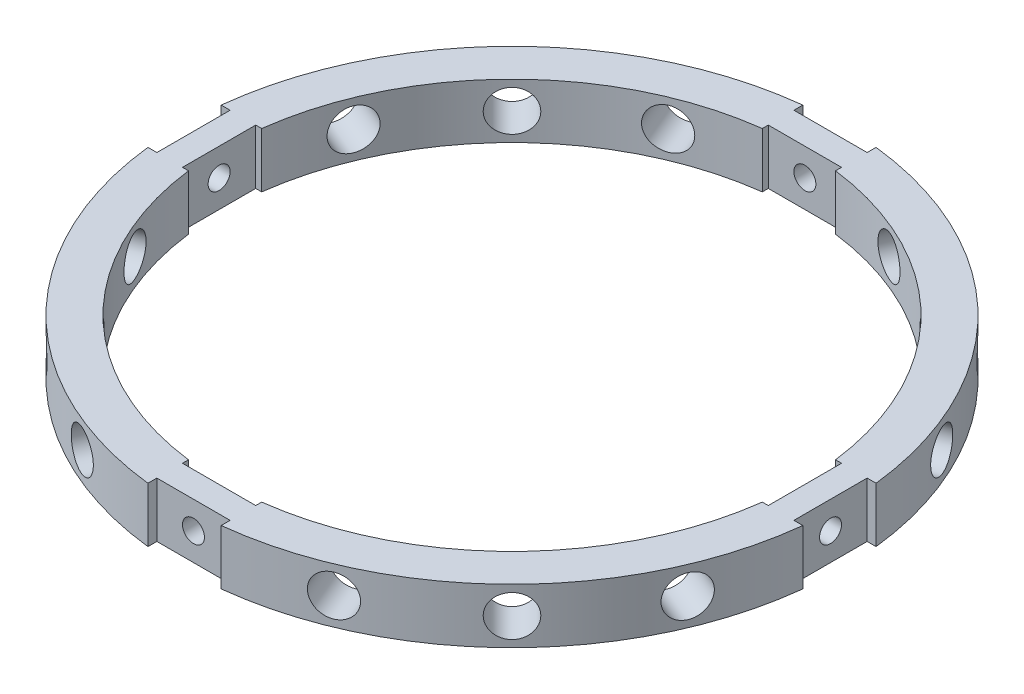
SolidWorks part; units mm, degrees
other "Markup1"
sketch "Sketch19"
material "1060 Alloy"
ref_plane "Front Plane" through (0, 0, 0) normal (0, 0, 1) x (1, 0, 0)
ref_plane "Top Plane" through (0, 0, 0) normal (0, 1, 0) x (1, 0, 0)
ref_plane "Right Plane" through (0, 0, 0) normal (1, 0, 0) x (0, 0, -1)
sketch "Sketch1" plane through (0, 0, 0) normal (0, 1, 0) x (1, 0, 0)
  circle A0 centre (0, 0) radius 90
  circle A1 centre (0, 0) radius 79
  dimension "OuterDiameter" = 180
  dimension "InnerDiameter" = 158
extrude "Boss-Extrude1" add sketch "Sketch1" along normal blind 7.5 and the other way blind 7.5
sketch "Sketch5" plane through (0, 7.5, 0) normal (0, 1, 0) x (1, 0, 0)
  line L0 (0, 0) -> (53.7588, 53.7588) construction
  line L1 (0.2616, 0.2616) -> (60.0121, 60.0121) construction
  line L2 (-121.3123, 0) -> (150.1577, 0) construction
  circle A0 centre (60.0121, 60.0121) radius 3
  circle A1 centre (60.0121, -59.4889) radius 3
  circle A2 centre (-59.4889, -59.4889) radius 3
  circle A3 centre (-59.4889, 60.0121) radius 3
  dimension "MountingBoltDiameter" = 6
  dimension "D2" = 84.5
  dimension "D3" = 45
sketch "Sketch6" plane through (0, 7.5, 0) normal (0, 1, 0) x (1, 0, 0)
  line L0 (0, -83.4209) -> (0, 77.0416) construction
  line L1 (-88.8703, 0) -> (103.6253, 0) construction
  line L2 (-10, -87) -> (10, -87)
  line L3 (-10, 90) -> (10, 90)
  line L4 (-10, 90) -> (-10, 87)
  line L5 (-10, 87) -> (10, 87)
  line L6 (10, 90) -> (10, 87)
  line L7 (-10, 90) -> (10, 87) construction
  line L8 (-10, 87) -> (10, 90) construction
  line L9 (10, -90) -> (10, -87)
  line L10 (-10, -90) -> (10, -90)
  line L11 (-10, -90) -> (-10, -87)
  line L12 (0, 0) -> (60.635, 60.635) construction
  line L13 (87, -10) -> (87, 10)
  line L14 (90, 10) -> (87, 10)
  line L15 (90, -10) -> (90, 10)
  line L16 (90, -10) -> (87, -10)
  line L17 (-90, -10) -> (-87, -10)
  line L18 (-90, -10) -> (-90, 10)
  line L19 (-90, 10) -> (-87, 10)
  line L20 (-87, -10) -> (-87, 10)
  point P5 (0, 88.5)
  point P10 (0, 90)
  dimension "RailWidth" = 20
  dimension "D1" = 90
  dimension "D2" = 3
extrude "Cut-Extrude4" cut sketch "Sketch6" against normal through all
sketch "Sketch7" plane through (-87, 0, 0) normal (-1, 0, 0) x (0, 0, 1)
  line L0 (0, 14.1508) -> (0, -8.7308) construction
  line L1 (-87, 0) -> (87, 0) construction
  line L2 (-87, -7.5) -> (-87, 7.5) construction
  line L3 (87, -7.5) -> (87, 7.5) construction
  circle A1 centre (0, 0) radius 3
  dimension "D1" = 6
extrude "Cut-Extrude5" cut sketch "Sketch7" against normal through all
sketch "Sketch12" plane through (0, 0, 87) normal (0, 0, 1) x (1, 0, 0)
  line L0 (0, 13.7216) -> (0, -16.0459) construction
  line L1 (-75.3828, 0) -> (78.5537, 0) construction
  circle A1 centre (0, 0) radius 3
  dimension "D1" = 6
extrude "Cut-Extrude8" cut sketch "Sketch12" against normal through all
sketch "Sketch13" plane through (0, 7.5, 0) normal (0, 1, 0) x (1, 0, 0)
  line L0 (0, -87.0356) -> (0, 86.4553) construction
  line L1 (-98.9563, 0) -> (122.4152, 0) construction
  line L2 (0, 0) -> (96.5387, 96.5387) construction
  line L3 (-10, -80) -> (10, -80)
  line L4 (-10, -80) -> (-10, -77)
  line L5 (-10, -77) -> (10, -77)
  line L6 (10, -80) -> (10, -77)
  line L7 (-10, -80) -> (10, -77) construction
  line L8 (-10, -77) -> (10, -80) construction
  line L9 (-10, 77) -> (10, 77)
  line L10 (10, 80) -> (10, 77)
  line L11 (-10, 80) -> (10, 80)
  line L12 (-10, 80) -> (-10, 77)
  line L13 (-77, -10) -> (-77, 10)
  line L14 (-80, 10) -> (-77, 10)
  line L15 (-80, -10) -> (-80, 10)
  line L16 (-80, -10) -> (-77, -10)
  line L17 (80, -10) -> (77, -10)
  line L18 (80, -10) -> (80, 10)
  line L19 (80, 10) -> (77, 10)
  line L20 (77, -10) -> (77, 10)
  point P7 (0, -78.5)
  dimension "D1" = 20
  dimension "D3" = 77
  dimension "D2" = 80
  dimension "D4" = 45
extrude "Cut-Extrude9" cut sketch "Sketch13" against normal through all
sketch "Sketch14" plane through (0, 7.5, 0) normal (0, 1, 0) x (1, 0, 0)
  line L0 (0, 98.1591) -> (0, -98.1685) construction
  line L1 (-142.6508, 0) -> (156.3484, 0) construction
  line L2 (0, -0.0047) -> (83.1508, 34.4375) construction
  line L3 (0, -0.0047) -> (34.4432, 83.1485) construction
  line L4 (-0.0047, 0) -> (83.1485, -34.4432) construction
  line L5 (-0.0047, 0) -> (34.4375, -83.1508) construction
  line L6 (0, 0.0047) -> (-34.4432, -83.1485) construction
  line L7 (0, 0.0047) -> (-83.1508, -34.4375) construction
  line L8 (0.0047, 0) -> (-83.1485, 34.4432) construction
  line L9 (0.0047, 0) -> (-34.4375, 83.1508) construction
  line L10 (63.6396, 63.6396) -> (-63.6396, -63.6396) construction
  line L11 (63.6396, -63.6396) -> (-63.6396, 63.6396) construction
  arc A0 (89.4427, 10) -> (10, 89.4427) centre (0, 0) ccw construction
  arc A1 (-89.4427, -10) -> (-10, -89.4427) centre (0, 0) ccw construction
  arc A2 (10, -89.4427) -> (89.4427, -10) centre (0, 0) ccw construction
  arc A3 (-10, 89.4427) -> (-89.4427, 10) centre (0, 0) ccw construction
  point P23 (0, 0)
  dimension "D1" = 22.5
  dimension "D2" = 22.5
  dimension "D3" = 4
ref_plane "Plane1" through (0.004, 0, -0.0017) normal (0.9239, 0, -0.3827) x (-0.3827, 0, -0.9239)
ref_plane "Plane2" through (0.0007, 0, -0.0017) normal (0.3827, 0, -0.9239) x (-0.9239, 0, -0.3827)
ref_plane "Plane3" through (-0.0017, 0, -0.004) normal (-0.3827, 0, -0.9239) x (-0.9239, 0, 0.3827)
ref_plane "Plane4" through (-0.0017, 0, -0.0007) normal (-0.9239, 0, -0.3827) x (-0.3827, 0, 0.9239)
sketch "Sketch15" plane through (0.004, 0, -0.0017) normal (0.9239, 0, -0.3827) x (-0.3827, 0, -0.9239)
  line L0 (-103.0218, 0) -> (121.7701, 0) construction
  circle A0 centre (0, 0) radius 5.565
  dimension "D1" = 11.13
extrude "Cut-Extrude10" cut sketch "Sketch15" against normal through all and the other way through all
sketch "Sketch16" plane through (0.0007, 0, -0.0017) normal (0.3827, 0, -0.9239) x (-0.9239, 0, -0.3827)
  line L0 (-116.6479, 0) -> (178.0546, 0) construction
  circle A0 centre (0, 0) radius 5.565
  dimension "D1" = 11.13
extrude "Cut-Extrude11" cut sketch "Sketch16" against normal through all and the other way through all
sketch "Sketch17" plane through (-0.0017, 0, -0.004) normal (-0.3827, 0, -0.9239) x (-0.9239, 0, 0.3827)
  line L0 (-115.4594, 0) -> (154.8622, 0) construction
  circle A0 centre (0, 0) radius 5.565
  dimension "D1" = 11.13
extrude "Cut-Extrude12" cut sketch "Sketch17" against normal through all and the other way through all
sketch "Sketch18" plane through (-0.0017, 0, -0.0007) normal (-0.9239, 0, -0.3827) x (-0.3827, 0, 0.9239)
  line L0 (-110.4319, 0) -> (111.3832, 0) construction
  circle A0 centre (0.4757, 0) radius 5.565
  dimension "D1" = 11.13
extrude "Cut-Extrude13" cut sketch "Sketch18" against normal through all and the other way through all
ref_plane "Plane5" through (0, 0, 0) normal (0.7071, 0, -0.7071) x (-0.7071, 0, -0.7071)
sketch "Sketch20" plane through (0, 0, 0) normal (0.7071, 0, -0.7071) x (-0.7071, 0, -0.7071)
  line L0 (-125.5135, 0) -> (138.902, 0) construction
  circle A0 centre (0, 0) radius 5.565
  dimension "D1" = 11.13
extrude "Cut-Extrude14" cut sketch "Sketch20" against normal through all and the other way through all
ref_plane "Plane6" through (0, 0, 0) normal (-0.7071, 0, -0.7071) x (-0.7071, 0, 0.7071)
sketch "Sketch21" plane through (0, 0, 0) normal (-0.7071, 0, -0.7071) x (-0.7071, 0, 0.7071)
  line L0 (-98.8665, 0) -> (107.0384, 0) construction
  circle A0 centre (0, 0) radius 5.565
  dimension "D1" = 11.13
extrude "Cut-Extrude15" cut sketch "Sketch21" against normal through all and the other way through all
equation "\"InternalDiameter\"= 158mm"
equation "\"ExternalDiameter\"= 180mm"
equation "\"InnerDiameter@Sketch1\"= \"InternalDiameter\""
equation "\"OuterDiameter@Sketch1\"= \"ExternalDiameter\""
equation "\"MountingBoltDiameter\"= 6mm"
equation "\"NumberOfMountingBolts\"= 4"
equation "\"MountingBoltDiameter@Sketch5\"= \"MountingBoltDiameter\""
equation "\"D1@Sketch5\"= \"NumberOfMountingBolts\""
equation "\"D2@Sketch5\"= 0.25 * ( \"InternalDiameter\" + \"ExternalDiameter\" )"
equation "\"RailBoltDiameter\"= 6mm"
equation "\"RailBoltSpacing\"= 12mm"
equation "\"RailWidth\"= 10mm"
equation "\"RailWidth@Sketch6\"= \"RailWidth\" * 2"
equation "\"D1@Sketch13\"= \"RailWidth\" * 2"
equation "\"RailDepth\"= 2mm"
equation "\"D3@Sketch13\"= \"InternalDiameter\" / 2 - \"RailDepth\""
equation "\"D2@Sketch13\"= \"InternalDiameter\" / 2 + \"RailDepth\" / 2"
equation "\"D1@Sketch6\"= \"ExternalDiameter\" / 2"
equation "\"D2@Sketch6\"= \"RailDepth\" * 1.5"
equation "\"TurnlockDiameter\"= 11.13mm"
equation "\"D1@Sketch15\"= \"TurnlockDiameter\""
equation "\"D1@Sketch16\"= \"D1@Sketch15\""
equation "\"D1@Sketch17\"= \"D1@Sketch16\""
equation "\"D1@Sketch18\"= \"D1@Sketch17\""
equation "\"D1@Sketch7\"= \"RailBoltDiameter\""
equation "\"D1@Sketch12\"= \"D1@Sketch7\""
equation "\"D1@Sketch20\"= \"D1@Sketch18\""
equation "\"D1@Sketch21\"= \"D1@Sketch20\""
